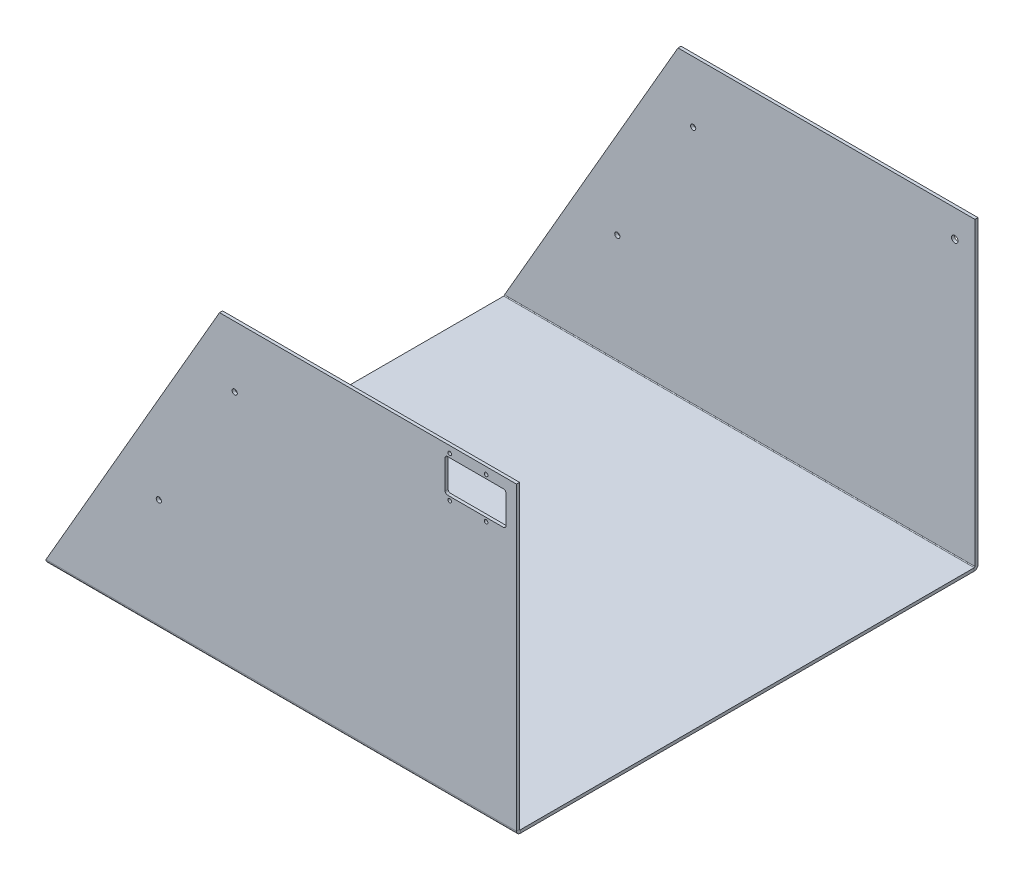
SolidWorks part; units mm, degrees
note: The reader was unsure of these and kept them because the rebuilt part matched: flange length of "Edge-Flange1", "Edge-Flange2".
ref_plane "Front Plane" through (0, 0, 0) normal (0, 0, 1) x (1, 0, 0)
ref_plane "Top Plane" through (0, 0, 0) normal (0, 1, 0) x (1, 0, 0)
ref_plane "Right Plane" through (0, 0, 0) normal (1, 0, 0) x (0, 0, -1)
sketch "Sketch7" plane through (0, 0, 0) normal (0, 0, 1) x (1, 0, 0)
  line L0 (0, 0) -> (0, 137.1901) construction
  line L1 (0, 0) -> (124.5467, 0) construction
  line L2 (-309.908, 0) -> (-195.603, 197.9822)
  line L3 (0, 0) -> (-309.908, 0)
  line L4 (0, 0) -> (0, 197.9822)
  line L5 (0, 197.9822) -> (-195.603, 197.9822)
  line L7 (-262.1812, 82.6654) -> (0, 0) construction
  line L8 (-234.6947, 73.999) -> (-195.603, 197.9822) construction
  line L9 (-228.8921, 140.3238) -> (0, 68.1544) construction
  dimension "D1" = 60
  dimension "D2" = 17.5
  dimension "D3" = 130
  dimension "D4" = 65
  dimension "D5" = 240
base flange "Base-Flange2" sketch "Sketch7" thickness 2 reverse thickness direction no parameters "D1"=2
edge flange "Edge-Flange1" sketch "Sketch14" flange angle 90 flange length 300 flange position bend outside bend radius 0.5 thickness 2 parameters "D6"=10
sketch "Sketch14" plane through (0, 0, -2) normal (0, -1, 0) x (-1, 0, 0)
  line L2 (0, 0) -> (0, 300)
  line L3 (0, 300) -> (309.908, 300)
  line L4 (309.908, 300) -> (309.908, 0)
  line L5 (309.908, 0) -> (0, 0) construction
  line L6 (309.908, 0) -> (0, 0)
bend "EdgeBend1" bend radius 0.5 bend angle 90 parameters "D5"=1
edge flange "Edge-Flange2" sketch "Sketch21" flange angle 90 flange length 272 flange position material outside bend radius 0.5 thickness 2 parameters "D6"=10
sketch "Sketch21" plane through (0, -0.5, -302) normal (0, 0, 1) x (1, 0, 0)
  line L2 (-309.908, 0) -> (-309.908, 270)
  line L3 (-309.908, 270) -> (0, 270)
  line L4 (0, 270) -> (0, 0)
  line L6 (0, 0) -> (-309.908, 0) construction
  line L7 (0, 0) -> (-309.908, 0)
bend "EdgeBend2" bend radius 0.5 bend angle 90 parameters "D5"=2
sketch "Sketch23" plane through (0, 0, -302) normal (0, 0, 1) x (1, 0, 0)
  line L0 (-29.8107, 26.2395) -> (-29.8107, 163.4296) construction
  line L1 (-29.8107, 26.2395) -> (94.736, 26.2395) construction
  line L2 (-309.908, 0) -> (-195.603, 197.9822)
  line L3 (0, 0) -> (-309.908, 0) construction
  line L4 (0, 0) -> (0, 197.9822)
  line L5 (0, 197.9822) -> (-195.603, 197.9822)
  line L6 (-309.908, 0) -> (-328.4125, -22.7822)
  line L7 (-262.1812, 82.6654) -> (0, 0) construction
  line L8 (-234.6947, 73.999) -> (-195.603, 197.9822) construction
  line L9 (-228.8921, 140.3238) -> (0, 68.1544) construction
  line L10 (-328.4125, -22.7822) -> (15.915, -38.5353)
  line L11 (15.915, -38.5353) -> (0, 0)
  dimension "D1" = 60
  dimension "D2" = 17.5
  dimension "D4" = 65
  dimension "D5" = 240
extrude "Cut-Extrude3" cut sketch "Sketch23" against normal through all flip side to cut
ref_plane "Plane3" through (0, 0, -152) normal (0, 0, 1) x (1, 0, 0)
hole_wizard "M3 Clearance Hole1" positions "Sketch49" profile "Sketch48" hole size "M3" standard "ANSI Metric"
sketch "Sketch49" plane through (0, 0, -304) normal (0, 0, -1) x (-1, 0, 0)
  line L0 (60375.8546, -190669.3912) -> (-59945.5569, 190941.3723) construction
  line L1 (262.1812, 82.6654) -> (0, 0) construction
  point P0 (235.5969, 71.1378)
  dimension "D1" = 3
sketch "Sketch48" plane through (-235.5969, 71.1378, -304) normal (1, 0, 0) x (0, 1, 0)
  line L0 (0, 0) -> (0, 304)
  line L1 (0, 304) -> (1.7, 304)
  line L2 (1.7, 304) -> (1.7, 0)
  line L5 (1.7, 0) -> (0, 0)
  line L11 (0, -6.35) -> (0, 107.95) construction
  dimension "Thru Hole Dia." = 3.4
  dimension "Thru Hole Depth" = 304
mirror "Mirror3" about plane through (0, 0, -152) normal (0, 0, 1) of "M3 Clearance Hole1"
sketch "Sketch50" plane through (0, 0, 0) normal (0, 0, 1) x (1, 0, 0)
  line L0 (0.5, 179.9822) -> (-56.2895, 179.9822) construction
  line L2 (-14, 179.9822) -> (-14, 211.4763) construction
  line L3 (-20, 193.4822) -> (-28, 193.4822) construction
  line L4 (-6.25, 193.4822) -> (17.75, 193.4822) construction
  line L7 (-47, 190.9822) -> (-7, 190.9822)
  line L8 (-47, 190.9822) -> (-47, 168.9822)
  line L9 (-47, 168.9822) -> (-7, 168.9822)
  line L10 (-7, 190.9822) -> (-7, 168.9822)
  circle A0 centre (-14, 179.9822) radius 11 construction
  circle A1 centre (-20, 193.4822) radius 1.2
  circle A2 centre (-20, 166.4822) radius 1.2
  circle A3 centre (-28, 193.4822) radius 1.2 construction
  circle A4 centre (-28, 166.4822) radius 1.2 construction
  circle A5 centre (-36, 193.4822) radius 1.2 construction
  circle A6 centre (-36, 166.4822) radius 1.2 construction
  circle A7 centre (-44, 193.4822) radius 1.2
  circle A8 centre (-44, 166.4822) radius 1.2
  circle A9 centre (-49.25, 187.9822) radius 1.2 construction
  circle A10 centre (-49.25, 171.9822) radius 1.2 construction
  dimension "D3" = 22
  dimension "D4" = 2.4
  dimension "D10" = 3
  dimension "D2" = 4.5
  dimension "D5" = 44
  dimension "D6" = 27
  dimension "D7" = 2.5
  dimension "D9" = 2.5
  dimension "D11" = 24
  dimension "D12" = 40
  dimension "D13" = 5.5
  dimension "D14" = 5.25
  dimension "D15" = 33
  dimension "D8" = 4
extrude "Cut-Extrude5" cut sketch "Sketch50" against normal blind 10
fillet "Fillet1" radius 1.5 4 edges at (-7, 168.9822, -1) (-47, 168.9822, -1) (-7, 190.9822, -1) (-47, 190.9822, -1)
hole_wizard "M4 Clearance Hole2" positions "Sketch54" profile "Sketch53" hole size "M4" standard "ANSI Metric" end condition up to next
sketch "Sketch54" plane through (0, 0, -304) normal (0, 0, -1) x (-1, 0, 0)
  line L0 (0, 197.9822) -> (195.603, 197.9822) construction
  line L1 (0, 0) -> (0, 197.9822) construction
  point P0 (13.3, 179.9822)
  dimension "D1" = 18
  dimension "D2" = 13.3
sketch "Sketch53" plane through (-13.3, 179.9822, -304) normal (1, 0, 0) x (0, 1, 0)
  line L0 (0, 0) -> (0, 2)
  line L1 (0, 2) -> (2.15, 2)
  line L2 (2.15, 2) -> (2.15, 0)
  line L5 (2.15, 0) -> (0, 0)
  line L11 (0, -6.35) -> (0, 107.95) construction
  dimension "Thru Hole Dia." = 4.3
  dimension "Thru Hole Depth" = 2
sketch "Sketch55" plane through (0, 0, -304) normal (0, 0, -1) x (-1, 0, 0)
  line L0 (235.5969, 71.1378) -> (260.5267, 85.5311) construction
  line L1 (309.908, 0) -> (195.603, 197.9822) construction
sketch "Sketch58" plane through (0, 0, -304) normal (0, 0, -1) x (-1, 0, 0)
  line L4 (162.3632, 197.9822) -> (276.6683, 0) construction
  line L5 (0, 197.9822) -> (195.603, 197.9822) construction
  line L6 (0, 0) -> (309.908, 0) construction
  line L8 (309.908, 0) -> (195.603, 197.9822) construction
  line L9 (195.603, 197.9822) -> (170.6732, 183.5889) construction
  line L10 (195.603, 197.9822) -> (309.908, 0) construction
hole_wizard "M3 Clearance Hole2" positions "Sketch62" profile "Sketch61" hole size "M3" standard "ANSI Metric"
sketch "Sketch62" plane through (0, 0, -304) normal (0, 0, -1) x (-1, 0, 0)
  line L0 (162.3632, 197.9822) -> (276.6683, 0) construction
  point P0 (185.6048, 157.7266)
  dimension "D1" = 29.8632
sketch "Sketch61" plane through (-185.6048, 157.7266, -304) normal (1, 0, 0) x (0, 1, 0)
  line L0 (0, 0) -> (0, 304)
  line L1 (0, 304) -> (1.7, 304)
  line L2 (1.7, 304) -> (1.7, 0)
  line L5 (1.7, 0) -> (0, 0)
  line L11 (0, -6.35) -> (0, 107.95) construction
  dimension "Thru Hole Dia." = 3.4
  dimension "Thru Hole Depth" = 304
mirror "Mirror4" about plane through (0, 0, -152) normal (0, 0, 1) of "M3 Clearance Hole2"
sketch "Bend-Lines3" [suppressed] plane through (0, 0, 0) normal (0, 1, 0) x (1, 0, 0)
sketch "Bounding-Box3" [suppressed] plane through (0, 0, 0) normal (0, 1, 0) x (1, 0, 0)
sheet metal parameters "Sheet-Metal2" thickness 2 parameters "D1"=0.7366
flat pattern "Flat-Pattern2" [suppressed]
sketch "Bend-Lines4" plane through (0, 0, 0) normal (0, 1, 0) x (1, 0, 0)
sketch3d "Bounding-Box4" [suppressed]
  line L0 (309.908, 0, 0) -> (0, 0, 0) construction
  line L1 (309.908, 197.9822, 0) -> (0, 197.9822, 0) construction
  line L2 (309.908, 0, 0) -> (309.908, 197.9822, 0) construction
  line L3 (0, 0, 0) -> (0, 197.9822, 0) construction
sheet metal parameters "Sheet-Metal3" thickness 2 parameters "D1"=0.7366
flat pattern "Flat-Pattern2"
sketch "Bend-Lines4" plane through (0, 0, 0) normal (0, 0, 1) x (1, 0, 0)
  line L0 (-309.908, -2.3562) -> (0, -2.3562) construction
  line L1 (-309.908, -2.3562) -> (0, -2.3562) construction
sketch3d "Bounding-Box4" [suppressed]
  line L0 (0, 197.9822, 0) -> (0, -300.7124, 0) construction
  line L1 (-309.908, 197.9822, 0) -> (-309.908, -300.7124, 0) construction
  line L2 (0, 197.9822, 0) -> (-309.908, 197.9822, 0) construction
  line L3 (0, -300.7124, 0) -> (-309.908, -300.7124, 0) construction
bend of the flat pattern "Flatten-<EdgeBend1>1"
sheet metal parameters "Sheet-Metal4" thickness 2 parameters "D1"=0.7366
flat pattern "Flat-Pattern2" [suppressed]
sketch "Bend-Lines4" plane through (0, 0, 0) normal (0, 0, 1) x (1, 0, 0)
  line L0 (-309.908, -2.3562) -> (0, -2.3562) construction
  line L1 (-309.908, -2.3562) -> (0, -2.3562) construction
  line L2 (-309.908, -303.0686) -> (0, -303.0686) construction
  line L3 (-309.908, -303.0686) -> (0, -303.0686) construction
sketch3d "Bounding-Box4" [suppressed]
  line L0 (0, 197.9822, 0) -> (0, -573.4248, 0) construction
  line L1 (-309.908, 197.9822, 0) -> (-309.908, -573.4248, 0) construction
  line L2 (0, 197.9822, 0) -> (-309.908, 197.9822, 0) construction
  line L3 (0, -573.4248, 0) -> (-309.908, -573.4248, 0) construction
bend of the flat pattern "Flatten-<EdgeBend1>1"
bend of the flat pattern "Flatten-<EdgeBend2>1"
sketch "Sketch23-1" [suppressed] plane through (0, -305.4248, -2) normal (0, 0, -1) x (1, 0, 0)
  line L0 (-29.8107, 26.2395) -> (-29.8107, 163.4296) construction
  line L1 (-29.8107, 26.2395) -> (94.736, 26.2395) construction
  line L2 (-309.908, 0) -> (-195.603, 197.9822)
  line L3 (0, 0) -> (-309.908, 0)
  line L4 (0, 0) -> (0, 197.9822)
  line L5 (0, 197.9822) -> (-195.603, 197.9822)
  line L7 (-262.1812, 82.6654) -> (0, 0) construction
  line L8 (-234.6947, 73.999) -> (-195.603, 197.9822) construction
  line L9 (-228.8921, 140.3238) -> (0, 68.1544) construction
  dimension "D1" = 60
  dimension "D2" = 17.5
  dimension "D3" = 130
  dimension "D4" = 65
  dimension "D5" = 240
sheet metal parameters "Sheet-Metal8" thickness 2 parameters "D1"=0.7366
flat pattern "Flat-Pattern2"
sketch "Bend-Lines7" plane through (0, 0, 0) normal (0, 0, 1) x (1, 0, 0)
  line L0 (0, -301.4978) -> (-309.908, -301.4978) construction
  line L1 (-309.908, -2.3562) -> (0, -2.3562) construction
  line L2 (0, -301.4978) -> (-309.908, -301.4978) construction
  line L3 (-309.908, -2.3562) -> (0, -2.3562) construction
sketch3d "Bounding-Box7" [suppressed]
  line L0 (0, 197.9822, 0) -> (0, -302.2832, 0) construction
  line L1 (-309.908, 197.9822, 0) -> (-309.908, -302.2832, 0) construction
  line L2 (0, 197.9822, 0) -> (-309.908, 197.9822, 0) construction
  line L3 (0, -302.2832, 0) -> (-309.908, -302.2832, 0) construction
bend of the flat pattern "Flatten-<EdgeBend2>3"
bend of the flat pattern "Flatten-<EdgeBend1>2"
sheet metal parameters "Sheet-Metal9" thickness 2 parameters "D1"=0.7366
flat pattern "Flat-Pattern2"
sketch "Bend-Lines8" plane through (0, 0, 0) normal (0, 1, 0) x (1, 0, 0)
sketch3d "Bounding-Box8" [suppressed]
  line L0 (-309.908, 0, 0) -> (0, 0, 0) construction
  line L1 (-309.908, 197.9822, 0) -> (0, 197.9822, 0) construction
  line L2 (-309.908, 0, 0) -> (-309.908, 197.9822, 0) construction
  line L3 (0, 0, 0) -> (0, 197.9822, 0) construction
sheet metal parameters "Sheet-Metal16" thickness 2 parameters "D1"=0.7366
flat pattern "Flat-Pattern2" [suppressed]
sketch "Bend-Lines4" plane through (0, 0, 0) normal (0, 0, 1) x (1, 0, 0)
  line L0 (-309.908, -2.3562) -> (0, -2.3562) construction
  line L1 (-309.908, -2.3562) -> (0, -2.3562) construction
  line L2 (-309.908, -303.0686) -> (0, -303.0686) construction
  line L3 (-309.908, -303.0686) -> (0, -303.0686) construction
sketch3d "Bounding-Box4" [suppressed]
  line L0 (0, 197.9822, 0) -> (0, -573.4248, 0) construction
  line L1 (-309.908, 197.9822, 0) -> (-309.908, -573.4248, 0) construction
  line L2 (0, 197.9822, 0) -> (-309.908, 197.9822, 0) construction
  line L3 (0, -573.4248, 0) -> (-309.908, -573.4248, 0) construction
bend of the flat pattern "Flatten-<EdgeBend1>1"
bend of the flat pattern "Flatten-<EdgeBend2>1"
sketch "Sketch23-1" [suppressed] plane through (0, -305.4248, -2) normal (0, 0, -1) x (1, 0, 0)
  line L0 (-29.8107, 26.2395) -> (-29.8107, 163.4296) construction
  line L1 (-29.8107, 26.2395) -> (94.736, 26.2395) construction
  line L2 (-309.908, 0) -> (-195.603, 197.9822)
  line L3 (0, 0) -> (-309.908, 0)
  line L4 (0, 0) -> (0, 197.9822)
  line L5 (0, 197.9822) -> (-195.603, 197.9822)
  line L7 (-262.1812, 82.6654) -> (0, 0) construction
  line L8 (-234.6947, 73.999) -> (-195.603, 197.9822) construction
  line L9 (-228.8921, 140.3238) -> (0, 68.1544) construction
  dimension "D1" = 60
  dimension "D2" = 17.5
  dimension "D3" = 130
  dimension "D4" = 65
  dimension "D5" = 240
sheet metal parameters "Sheet-Metal18" thickness 2 parameters "D1"=0.7366
flat pattern "Flat-Pattern2"
sketch "Bend-Lines8" plane through (0, 0, -302) normal (0, 0, 1) x (1, 0, 0)
  line L0 (-311.9486, 1.1781) -> (-197.6435, 199.1603) construction
  line L1 (-311.9486, 1.1781) -> (-197.6435, 199.1603) construction
  line L2 (-197.6435, -504.585) -> (-311.9486, -306.6029) construction
  line L3 (0, -2.3562) -> (-309.908, -2.3562) construction
  line L4 (0, -303.0686) -> (-309.908, -303.0686) construction
  line L5 (-197.6435, -504.585) -> (-311.9486, -306.6029) construction
  line L6 (0, -2.3562) -> (-309.908, -2.3562) construction
  line L7 (0, -303.0686) -> (-309.908, -303.0686) construction
sketch3d "Bounding-Box8" [suppressed]
  line L0 (0, 210.8384, 0) -> (0, -516.2631, 0) construction
  line L1 (-332.1756, 210.8384, 0) -> (-332.1756, -516.2631, 0) construction
  line L2 (0, 210.8384, 0) -> (-332.1756, 210.8384, 0) construction
  line L3 (0, -516.2631, 0) -> (-332.1756, -516.2631, 0) construction
bend of the flat pattern "Flatten-<EdgeBend2>7"
bend of the flat pattern "Flatten-<EdgeBend1>6"
sheet metal parameters "Sheet-Metal19" thickness 2 parameters "D1"=0.7366
flat pattern "Flat-Pattern2"
sketch "Bend-Lines8" plane through (0, 0, -302) normal (0, 0, 1) x (1, 0, 0)
  line L0 (-311.9486, 1.1781) -> (-197.6435, 199.1603) construction
  line L1 (-311.9486, 1.1781) -> (-197.6435, 199.1603) construction
  line L2 (-197.6435, -504.585) -> (-311.9486, -306.6029) construction
  line L3 (0, -2.3562) -> (-309.908, -2.3562) construction
  line L4 (0, -303.0686) -> (-309.908, -303.0686) construction
  line L5 (-197.6435, -504.585) -> (-311.9486, -306.6029) construction
  line L6 (0, -2.3562) -> (-309.908, -2.3562) construction
  line L7 (0, -303.0686) -> (-309.908, -303.0686) construction
sketch3d "Bounding-Box8" [suppressed]
  line L0 (0, 210.8384, 0) -> (0, -516.2631, 0) construction
  line L1 (-332.1756, 210.8384, 0) -> (-332.1756, -516.2631, 0) construction
  line L2 (0, 210.8384, 0) -> (-332.1756, 210.8384, 0) construction
  line L3 (0, -516.2631, 0) -> (-332.1756, -516.2631, 0) construction
bend of the flat pattern "Flatten-<EdgeBend2>7"
bend of the flat pattern "Flatten-<EdgeBend1>6"
sheet metal parameters "Sheet-Metal20" thickness 2 parameters "D1"=0.7366
flat pattern "Flat-Pattern2"
sketch "Bend-Lines8" plane through (0, 0, -302) normal (0, 0, 1) x (1, 0, 0)
  line L0 (-311.9486, 1.1781) -> (-197.6435, 199.1603) construction
  line L1 (-311.9486, 1.1781) -> (-197.6435, 199.1603) construction
  line L2 (-197.6435, -504.585) -> (-311.9486, -306.6029) construction
  line L3 (0, -2.3562) -> (-309.908, -2.3562) construction
  line L4 (0, -303.0686) -> (-309.908, -303.0686) construction
  line L5 (-197.6435, -504.585) -> (-311.9486, -306.6029) construction
  line L6 (0, -2.3562) -> (-309.908, -2.3562) construction
  line L7 (0, -303.0686) -> (-309.908, -303.0686) construction
sketch3d "Bounding-Box8" [suppressed]
  line L0 (0, 210.8384, 0) -> (0, -516.2631, 0) construction
  line L1 (-332.1756, 210.8384, 0) -> (-332.1756, -516.2631, 0) construction
  line L2 (0, 210.8384, 0) -> (-332.1756, 210.8384, 0) construction
  line L3 (0, -516.2631, 0) -> (-332.1756, -516.2631, 0) construction
bend of the flat pattern "Flatten-<EdgeBend2>7"
bend of the flat pattern "Flatten-<EdgeBend1>6"
sheet metal parameters "Sheet-Metal22" thickness 2 parameters "D1"=0.7366
flat pattern "Flat-Pattern2"
sketch "Bend-Lines8" plane through (0, 0, -302) normal (0, 0, 1) x (1, 0, 0)
  line L3 (0, -1.1781) -> (-309.908, -1.1781) construction
  line L4 (0, -302.5343) -> (-309.908, -302.5343) construction
  line L6 (0, -1.1781) -> (-309.908, -1.1781) construction
  line L7 (0, -302.5343) -> (-309.908, -302.5343) construction
sketch3d "Bounding-Box8" [suppressed]
  line L0 (0, 197.9822, 0) -> (0, -501.6946, 0) construction
  line L1 (-309.908, 197.9822, 0) -> (-309.908, -501.6946, 0) construction
  line L2 (0, 197.9822, 0) -> (-309.908, 197.9822, 0) construction
  line L3 (0, -501.6946, 0) -> (-309.908, -501.6946, 0) construction
bend of the flat pattern "Flatten-<EdgeBend2>7"
bend of the flat pattern "Flatten-<EdgeBend1>6"
sheet metal parameters "Sheet-Metal23" thickness 2 parameters "D1"=0.7366
flat pattern "Flat-Pattern2"
sketch "Bend-Lines8" plane through (0, 0, -302) normal (0, 0, 1) x (1, 0, 0)
  line L3 (0, -1.1781) -> (-309.908, -1.1781) construction
  line L4 (0, -302.5343) -> (-309.908, -302.5343) construction
  line L6 (0, -1.1781) -> (-309.908, -1.1781) construction
  line L7 (0, -302.5343) -> (-309.908, -302.5343) construction
sketch3d "Bounding-Box8" [suppressed]
  line L0 (0, 197.9822, 0) -> (0, -501.6946, 0) construction
  line L1 (-309.908, 197.9822, 0) -> (-309.908, -501.6946, 0) construction
  line L2 (0, 197.9822, 0) -> (-309.908, 197.9822, 0) construction
  line L3 (0, -501.6946, 0) -> (-309.908, -501.6946, 0) construction
bend of the flat pattern "Flatten-<EdgeBend2>7"
bend of the flat pattern "Flatten-<EdgeBend1>6"
sheet metal parameters "Sheet-Metal24" thickness 2 parameters "D1"=0.7366
flat pattern "Flat-Pattern2"
sketch "Bend-Lines8" plane through (0, 0, -302) normal (0, 0, 1) x (1, 0, 0)
  line L3 (0, -1.1781) -> (-309.908, -1.1781) construction
  line L4 (0, -302.5343) -> (-309.908, -302.5343) construction
  line L6 (0, -1.1781) -> (-309.908, -1.1781) construction
  line L7 (0, -302.5343) -> (-309.908, -302.5343) construction
sketch3d "Bounding-Box8" [suppressed]
  line L0 (0, 197.9822, 0) -> (0, -501.6946, 0) construction
  line L1 (-309.908, 197.9822, 0) -> (-309.908, -501.6946, 0) construction
  line L2 (0, 197.9822, 0) -> (-309.908, 197.9822, 0) construction
  line L3 (0, -501.6946, 0) -> (-309.908, -501.6946, 0) construction
bend of the flat pattern "Flatten-<EdgeBend2>7"
bend of the flat pattern "Flatten-<EdgeBend1>6"
equation "\"length_edge_flange\" = 33.11mm"
equation "\"distance_fente_rampe\" = 158.61mm"
equation "\"distance_interieur\" = 300mm"
equation "\"longeur_interieur\"= 274.9mm"
equation "\"distance_trou\" = 28.82mm"
equation "\"hauteur_conteneur\"= 200mm"
